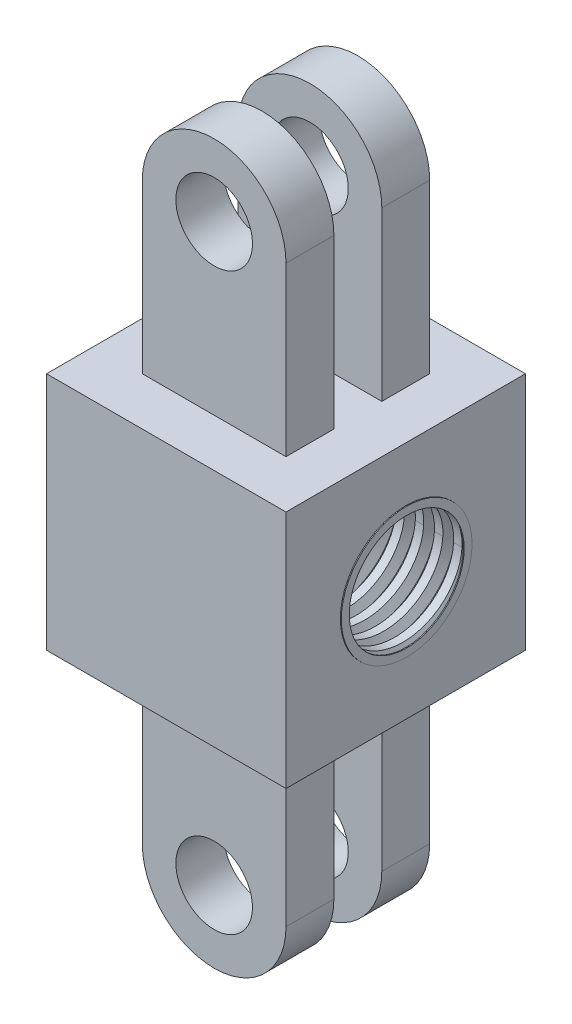
SolidWorks part; units mm, degrees
ref_plane "Front Plane" through (0, 0, 0) normal (0, 0, 1) x (1, 0, 0)
ref_plane "Top Plane" through (0, 0, 0) normal (0, 1, 0) x (1, 0, 0)
ref_plane "Right Plane" through (0, 0, 0) normal (1, 0, 0) x (0, 0, -1)
sketch "Sketch1" plane through (0, 0, 0) normal (0, 1, 0) x (1, 0, 0)
  line L1 (0, 0) -> (25, 0)
  line L2 (0, 0) -> (0, -25)
  line L3 (0, -25) -> (25, -25)
  line L4 (25, 0) -> (25, -25)
  dimension "D1" = 25
  dimension "D2" = 25
extrude "Boss-Extrude1" add sketch "Sketch1" along normal blind 25
sketch "Sketch2" plane through (0, 25, 0) normal (0, 1, 0) x (1, 0, 0)
  line L0 (0, -12.5) -> (48.3049, -12.5) construction
  line L1 (0, 0) -> (0, -25) construction
  line L2 (25, 0) -> (0, 0) construction
  line L3 (5, -5) -> (20, -5)
  line L4 (5, -5) -> (5, -10)
  line L5 (5, -10) -> (20, -10)
  line L6 (20, -5) -> (20, -10)
  line L9 (20, -20) -> (20, -15)
  line L10 (5, -15) -> (20, -15)
  line L11 (5, -20) -> (5, -15)
  line L12 (5, -20) -> (20, -20)
  dimension "D1" = 5
  dimension "D2" = 5
  dimension "D3" = 5
  dimension "D4" = 15
extrude "Boss-Extrude2" add sketch "Sketch2" along normal blind 17.5
sketch "Sketch3" plane through (0, 0, 20) normal (0, 0, 1) x (1, 0, 0)
  line L0 (5, 42.5) -> (20, 42.5) construction
  circle A0 centre (12.5, 42.5) radius 7.5
  circle A1 centre (12.5, 42.5) radius 4
  dimension "D1" = 8
extrude "Boss-Extrude4" add sketch "Sketch3" against normal up to surface (5 mm away) up to face at (12.5, 33.75, 15)
sketch "Sketch4" plane through (0, 0, 20) normal (0, 0, 1) x (1, 0, 0)
  line L0 (8.5, 42.5) -> (16.5, 42.5) construction
  circle A0 centre (12.5, 42.5) radius 4
extrude "Cut-Extrude1" cut sketch "Sketch4" against normal blind 21.5
sketch "Sketch5" plane through (0, 0, 5) normal (0, 0, -1) x (-1, 0, 0)
  line L0 (-8.5, 42.5) -> (-5, 42.5) construction
  line L1 (-20, 42.5) -> (-16.5, 42.5) construction
  line L2 (-8.5, 42.5) -> (-5, 42.5)
  line L3 (-20, 42.5) -> (-16.5, 42.5)
  circle A0 centre (-12.5, 42.5) radius 4 construction
  arc A1 (-5, 42.5) -> (-20, 42.5) centre (-12.5, 42.5) ccw construction
  circle A2 centre (-12.5, 42.5) radius 4
  arc A3 (-5, 42.5) -> (-20, 42.5) centre (-12.5, 42.5) ccw
  line M1 (-5, 42.5) -> (-8.5, 42.5)
  line M3 (-16.5, 42.5) -> (-20, 42.5)
extrude "Boss-Extrude5" add sketch "Sketch5" against normal up to surface (5 mm away) contours A3 A2 M1 M3 region at (12.5, 46.6677, 5) up to face at (12.5, 36, 10)
ref_plane "Plane1" through (0, 12.5, 0) normal (0, 1, 0) x (1, 0, 0)
mirror "Mirror1" about plane through (0, 12.5, 0) normal (0, 1, 0) of "Boss-Extrude5", "Cut-Extrude1", "Boss-Extrude4", "Boss-Extrude2", "Boss-Extrude1"
sketch "Sketch6" plane through (25, 0, 0) normal (1, 0, 0) x (0, 0, -1)
  line L0 (-25, 0) -> (0, 0) construction
  line L1 (0, 25) -> (0, 0) construction
  circle A0 centre (-12.5, 12.5) radius 6
  dimension "D3" = 12
  dimension "D1" = 12.5
  dimension "D2" = 12.5
extrude "Cut-Extrude2" cut sketch "Sketch6" against normal blind 63.5
thread "Thread2" pitch 1.5 method cut profile "Thread Profile3" start angle 0, offset 2, length 30, pitch 2, diameter 12
ref_plane "Plane4" through (27, 12.5, 18.5) normal (0, -1, 0) x (0, 0, 1)
sketch "Thread Profile3" plane through (27, 12.5, 18.5) normal (0, -1, 0) x (0, 0, 1)
  line L0 (0, 0) -> (0, 1.5) construction
  line L1 (0, 0) -> (0.8119, 0.4687)
  line L2 (0.8119, 0.4687) -> (0.8119, 0.6562)
  line L3 (0.8119, 0.6562) -> (0, 1.125)
  line L4 (0.8119, 0.5625) -> (0, 0.5625) construction
  line L11 (0, 0) -> (0, 1.125)
  point P2 (0, 0)
  dimension "Pitch" = 1.5
  dimension "Profile_Angle" = 60
  dimension "Profile_Land" = 0.1875
  dimension "Profile_Height" = 0.8119
sketch "Sketch7" plane through (25, 0, 0) normal (1, 0, 0) x (0, 0, -1)
  circle A0 centre (-12.5, 12.5) radius 6
  circle A1 centre (-12.5, 12.5) radius 6.8257
extrude "Boss-Extrude6" add sketch "Sketch7" along normal blind 0.1
